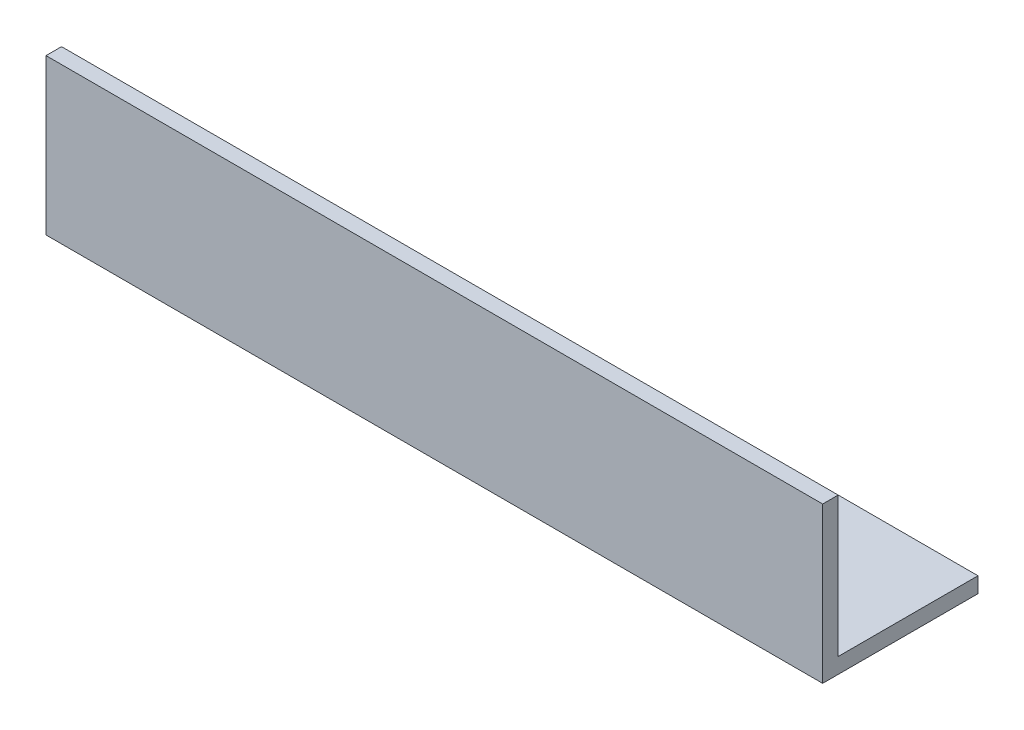
SolidWorks part; units mm, degrees
ref_plane "Спереди" through (0, 0, 0) normal (0, 0, 1) x (1, 0, 0)
ref_plane "Сверху" through (0, 0, 0) normal (0, 1, 0) x (1, 0, 0)
ref_plane "Справа" through (0, 0, 0) normal (1, 0, 0) x (0, 0, -1)
sketch "Эскиз1" plane through (0, 0, 0) normal (1, 0, 0) x (0, 0, -1)
  line L0 (0, 0) -> (0, 30)
  line L1 (0, 0) -> (30, 0)
extrude "Вытянуть-Тонкостенный1" add sketch "Эскиз1" along normal blind 150 thin thin type one direction reverse wall 3
sketch "Эскиз2" plane through (0, 0, 0) normal (0, -1, 0) x (1, 0, 0)
  line L0 (75, -35.357) -> (75, 2.5686) construction
  circle A0 centre (130, -15) radius 5
  circle A1 centre (100, -15) radius 5
  circle A2 centre (50, -15) radius 5
  circle A3 centre (20, -15) radius 5
  dimension "D1" = 2
extrude "Вырез-Вытянуть1" cut sketch "Эскиз2" against normal through all
